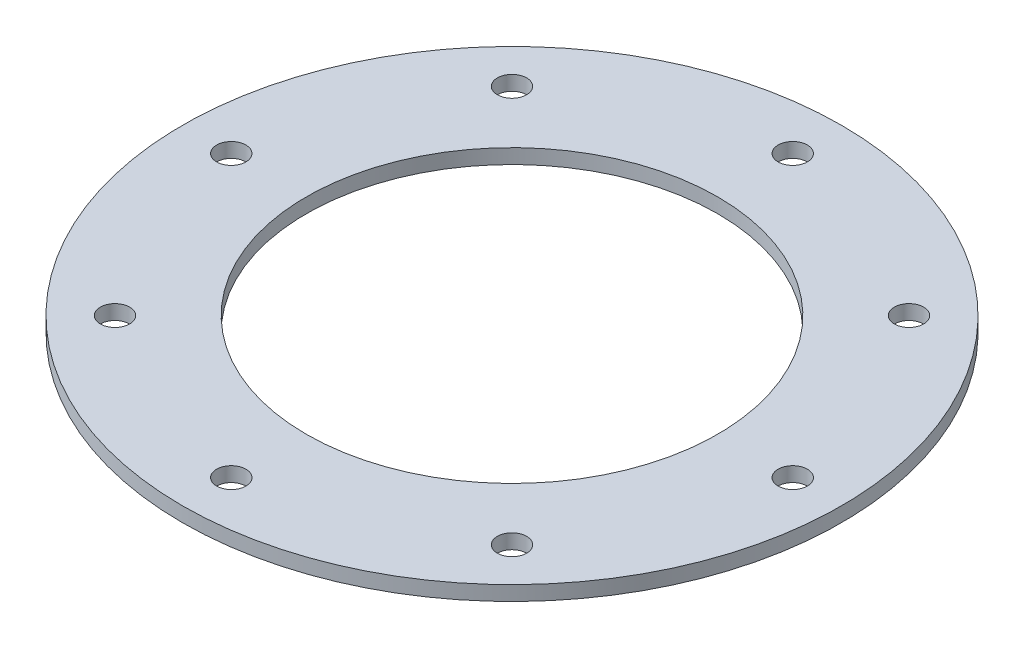
SolidWorks part; units mm, degrees
ref_plane "Front Plane" through (0, 0, 0) normal (0, 0, 1) x (1, 0, 0)
ref_plane "Top Plane" through (0, 0, 0) normal (0, 1, 0) x (1, 0, 0)
ref_plane "Right Plane" through (0, 0, 0) normal (1, 0, 0) x (0, 0, -1)
sketch "Sketch1" plane through (0, 0, 0) normal (0, 1, 0) x (1, 0, 0)
  circle A0 centre (0, 0) radius 135
  circle A1 centre (0, 0) radius 84.25
  dimension "D1" = 270
  dimension "D2" = 168.5
extrude "Boss-Extrude1" add sketch "Sketch1" along normal blind 6
sketch "Sketch2" plane through (0, 6, 0) normal (0, 1, 0) x (1, 0, 0)
  circle A0 centre (0, 115) radius 6
  circle A1 centre (81.3173, 81.3173) radius 6
  circle A2 centre (115, 0) radius 6
  circle A3 centre (81.3173, -81.3173) radius 6
  circle A4 centre (0, -115) radius 6
  circle A5 centre (-81.3173, -81.3173) radius 6
  circle A6 centre (-115, 0) radius 6
  circle A7 centre (-81.3173, 81.3173) radius 6
  point P4 (0, 0)
  point P19 (0, 0)
  dimension "D1" = 12
  dimension "D2" = 115
  dimension "D3" = 8
extrude "Cut-Extrude1" cut sketch "Sketch2" against normal through all
